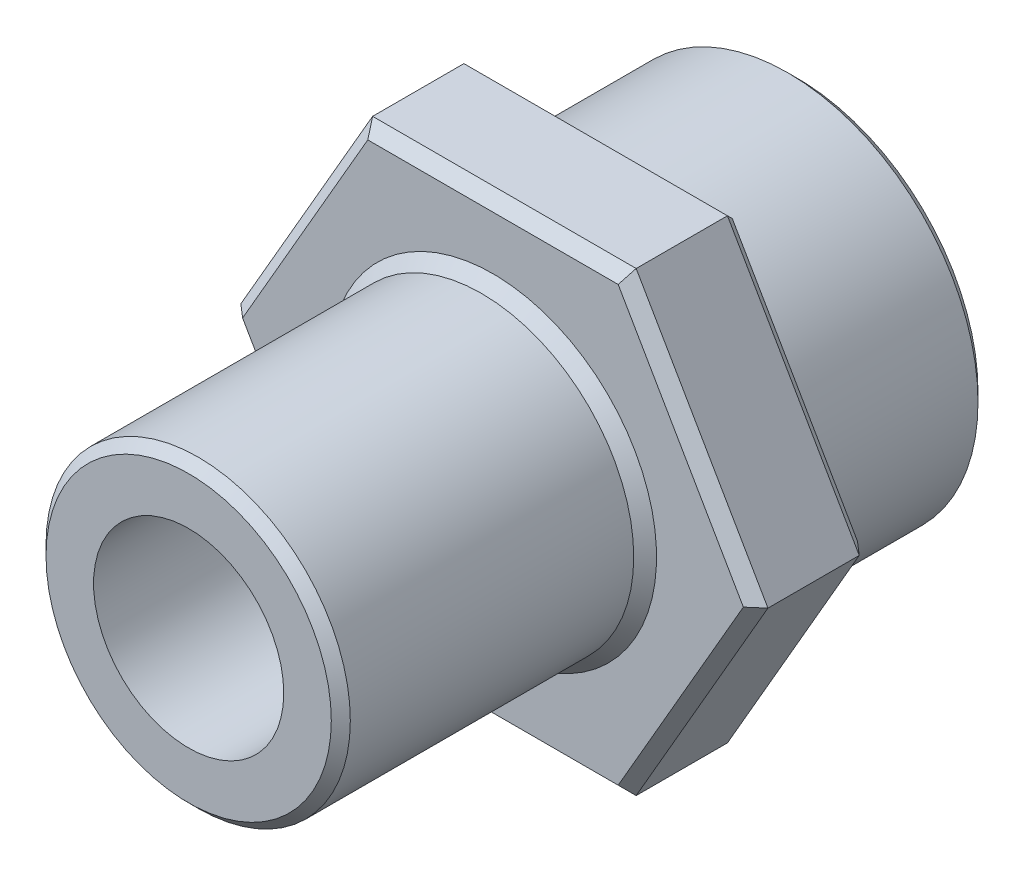
SolidWorks part; units mm, degrees
ref_plane "Front Plane" through (0, 0, 0) normal (0, 0, 1) x (1, 0, 0)
ref_plane "Top Plane" through (0, 0, 0) normal (0, 1, 0) x (1, 0, 0)
ref_plane "Right Plane" through (0, 0, 0) normal (1, 0, 0) x (0, 0, -1)
sketch "Sketch1" plane through (0, 0, 0) normal (0, 0, 1) x (1, 0, 0)
  circle A0 centre (0, 0) radius 4
  dimension "D1" = 8
extrude "Boss-Extrude1" add sketch "Sketch1" along normal blind 8
sketch "Sketch2" plane through (0, 0, 0) normal (0, 0, -1) x (-1, 0, 0)
  line L1 (-3.4641, 6) -> (-6.9282, 0)
  line L2 (-6.9282, 0) -> (-3.4641, -6)
  line L3 (-3.4641, -6) -> (3.4641, -6)
  line L4 (3.4641, -6) -> (6.9282, 0)
  line L5 (6.9282, 0) -> (3.4641, 6)
  line L6 (3.4641, 6) -> (-3.4641, 6)
  circle A0 centre (0, 0) radius 6 construction
  dimension "D1" = 12
extrude "Boss-Extrude2" add sketch "Sketch2" along normal blind 3
sketch "Sketch3" plane through (0, 0, -3) normal (0, 0, -1) x (-1, 0, 0)
  circle A0 centre (0, 0) radius 5
  dimension "D1" = 10
extrude "Boss-Extrude3" add sketch "Sketch3" along normal blind 5
sketch "Sketch4" plane through (0, 0, 8) normal (0, 0, 1) x (1, 0, 0)
  circle A0 centre (0, 0) radius 2.5
  dimension "D1" = 5
extrude "Cut-Extrude1" cut sketch "Sketch4" against normal through all
chamfer "Chamfer1" distance 0.3 angle 45 1 edges at (4, 0, 0)
chamfer "Chamfer2" distance 0.3 angle 45 1 edges at (2.5, 0, -8)
sketch "Sketch5" plane through (0, 0, 0) normal (0, 1, 0) x (1, 0, 0)
  line L0 (2.8, 8) -> (-2.8, 8) construction
  line L1 (-1.5, 8) -> (1.5, 8)
  line L2 (-1.5, 8) -> (-1.5, 5)
  line L3 (-1.5, 5) -> (1.5, 5)
  line L4 (1.5, 8) -> (1.5, 5)
  point P6 (0, 5)
  dimension "D1" = 3
  dimension "D2" = 3
extrude "Cut-Extrude2" cut sketch "Sketch5" against normal through all
chamfer "Chamfer3" distance 0.3 angle 45 12 edges at (5.1962, 3, 0) (5.1962, -3, 0) (0, -6, 0) (-5.1962, -3, 0) (-5.1962, 3, 0) (0, 6, 0) (-5.1962, 3, -3) (0, 6, -3) (5.1962, 3, -3) (-5.1962, -3, -3) (5.1962, -3, -3) (0, -6, -3)
chamfer "Chamfer4" distance 0.3 angle 45 5 edges at (1.5, -3.567, -8) (-1.5, -3.567, -8) (0, -5, -5) (-1.5, -4.7697, -6.5) (1.5, -4.7697, -6.5) first distance on face at (1.5, -3.1443, -6.71) first distance on face at (-1.5, -3.2172, -6.77) first distance on face at (0, -3.5674, -5)
chamfer "Chamfer5" distance 0.25 angle 45 2 edges at (0, 5, -8) (4, 0, 8)
